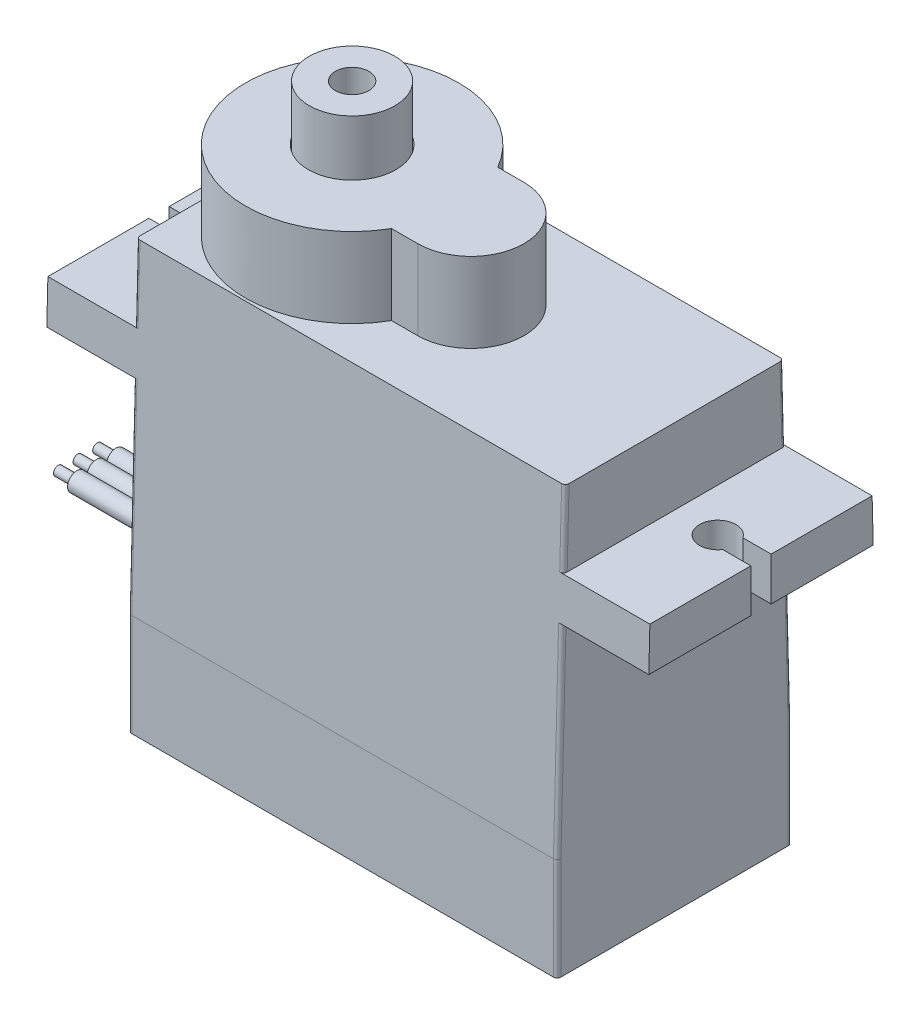
SolidWorks part; units mm, degrees
ref_plane "Front Plane" through (0, 0, 0) normal (0, 0, 1) x (1, 0, 0)
ref_plane "Top Plane" through (0, 0, 0) normal (0, 1, 0) x (1, 0, 0)
ref_plane "Right Plane" through (0, 0, 0) normal (1, 0, 0) x (0, 0, -1)
ref_axis "X-Axis" through (-88.99, 0, 0) along (1, 0, 0)
ref_axis "Y-Axis" through (0, 0, -88.99) along (0, 0, 1)
ref_axis "Z-Axis" through (0, 55, 0) along (0, -1, 0)
sketch "Sketch1" plane through (0, 0, 0) normal (0, 0, 1) x (1, 0, 0)
  line L0 (0, 0) -> (0, 12.96) construction
  line L1 (-7.1, 6.38) -> (15.93, 6.38)
  line L2 (-7.1, 6.38) -> (-7.1, 2.32)
  line L3 (-7.1, -16.34) -> (15.93, -16.34)
  line L4 (15.93, 6.38) -> (15.93, 2.32)
  line L5 (15.93, 2.32) -> (20.57, 2.32)
  line L6 (-11.74, 2.32) -> (-7.1, 2.32)
  line L7 (-11.74, 2.32) -> (-11.74, 0)
  line L8 (-11.74, 0) -> (-7.1, 0)
  line L9 (20.57, 2.32) -> (20.57, 0)
  line L10 (15.93, 0) -> (20.57, 0)
  line L11 (-7.1, 0) -> (-7.1, -16.34)
  line L12 (15.93, 0) -> (15.93, -16.34)
  line L14 (15.93, 0) -> (-7.1, 0) construction
  point P3 (4.415, 0)
  dimension "D1" = 2.32
  dimension "D2" = 32.31
  dimension "D3" = 23.03
  dimension "D4" = 16.34
  dimension "D5" = 22.72
  dimension "D6" = 7.1
  dimension "D7" = 15.93
  dimension "D10" = 29.3
  dimension "D11" = 4.415
extrude "Boss-Extrude1" add sketch "Sketch1" along normal mid plane 12.6
sketch "Sketch2" plane through (0, 6.38, 0) normal (0, 1, 0) x (1, 0, 0)
  line L0 (-1.375, 0) -> (5, 0) construction
  line L1 (3.5902, -2.85) -> (5, -2.85)
  line L2 (5, 2.85) -> (3.5902, 2.85)
  line L3 (-1.375, 0) -> (-7.1, 0) construction
  line L4 (5, 0) -> (7.85, 0) construction
  line L5 (-7.1, -6.3) -> (-7.1, 6.3) construction
  arc A0 (3.5902, 2.85) -> (3.5902, -2.85) centre (-1.375, 0) ccw
  arc A1 (5, -2.85) -> (5, 2.85) centre (5, 0) ccw
  dimension "D1" = 11.45
  dimension "D2" = 5.7
  dimension "D3" = 14.95
extrude "Boss-Extrude2" add sketch "Sketch2" along normal blind 4.28
sketch "Sketch11" plane through (-11.74, 0, 0) normal (-1, 0, 0) x (0, 0, 1)
  line L0 (-5.86, 6.38) -> (-6.3, -10.84)
  line L1 (0, 6.38) -> (-6.3, 6.38) construction
  line L2 (6.3, -16.34) -> (-6.3, -16.34) construction
  line L3 (-6.3, 0) -> (-6.3, -16.34) construction
  line L4 (-5.86, 6.38) -> (-6.3, 6.38)
  line L5 (-6.3, 6.38) -> (-6.3, -10.84)
  dimension "D1" = 5.86
  dimension "D2" = 5.5
extrude "Cut-Extrude4" cut sketch "Sketch11" against normal through all
mirror "Mirror1" about plane through (0, 0, 0) normal (0, 0, 1) of "Cut-Extrude4"
sketch "Sketch4" plane through (0, 0, 0) normal (0, 1, 0) x (1, 0, 0)
  line L0 (-7.1, 0) -> (-9.42, 0) construction
  line L1 (-11.74, -5.9637) -> (-11.74, 5.9637) construction
  line L2 (-10.2285, 0.545) -> (-11.74, 0.545)
  line L3 (-10.2285, 0.545) -> (-10.2285, -0.545)
  line L4 (-10.2285, -0.545) -> (-11.74, -0.545)
  line L5 (-11.74, 0.545) -> (-11.74, -0.545)
  line L8 (-9.42, 0) -> (-10.2285, 0) construction
  line L9 (-9.42, 0) -> (-11.74, 0) construction
  arc A0 (3.5902, 2.85) -> (3.5902, -2.85) centre (-1.375, 0) ccw construction
  circle A1 centre (-9.42, 0) radius 0.975
  dimension "D1" = 1.09
  dimension "D2" = 1.95
extrude "Cut-Extrude1" cut sketch "Sketch4" along normal through all contours A1 | L4 L5 L2 L3
sketch "Sketch14" plane through (0, 0.1538, 6.0191) normal (0, 0.0255, 0.9997) x (1, 0, 0)
  line L0 (4.415, -10.9974) -> (-7.1, -10.9974) construction
  line L1 (15.93, -10.9974) -> (-7.1, -10.9974) construction
ref_plane "Plane1" through (4.415, -10.84, 6.3) normal (-1, 0, 0) x (0, 0, 1)
mirror "Mirror2" about plane through (4.415, -10.84, 6.3) normal (-1, 0, 0) of "Cut-Extrude1"
sketch "Sketch5" plane through (0, -16.34, 0) normal (0, -1, 0) x (1, 0, 0)
  line L0 (15.93, 6.3) -> (-7.1, -6.3) construction
  line L17 (-5.46, 4.35) -> (14.29, 4.35) construction
  line L18 (-5.46, 4.35) -> (-5.46, -4.35) construction
  line L19 (-5.46, -4.35) -> (14.29, -4.35) construction
  line L20 (14.29, 4.35) -> (14.29, -4.35) construction
  line L21 (-5.46, 4.35) -> (14.29, -4.35) construction
  circle A0 centre (-5.46, 4.35) radius 1
  circle A1 centre (-5.46, -4.35) radius 1
  circle A2 centre (14.29, -4.35) radius 1
  circle A3 centre (14.29, 4.35) radius 1
  circle A4 centre (-5.46, 4.35) radius 0.975
  circle A5 centre (-5.46, -4.35) radius 0.975
  circle A6 centre (14.29, -4.35) radius 0.975
  circle A7 centre (14.29, 4.35) radius 0.975
  point P36 (4.415, 0)
  dimension "D1" = 0.025
  dimension "D4" = 1.95
  dimension "D5" = 19.75
  dimension "D6" = 8.7
extrude "Cut-Extrude2" cut sketch "Sketch5" against normal blind 1
sketch "Sketch6" plane through (-7.1, 0, 0) normal (-1, 0, 0) x (0, 0, 1)
  line L0 (-1.05, -11.34) -> (1.05, -11.34) construction
  line L1 (0, -11.84) -> (0, -16.34) construction
  line L3 (6.3, -16.34) -> (-6.3, -16.34) construction
  circle A0 centre (0, -11.34) radius 0.5
  circle A1 centre (1.05, -11.34) radius 0.5
  circle A2 centre (-1.05, -11.34) radius 0.5
  dimension "D3" = 1
  dimension "D1" = 4.5
  dimension "D2" = 2.1
extrude "Boss-Extrude4" add sketch "Sketch6" along normal blind 8
sketch "Sketch7" plane through (-15.1, 0, 0) normal (-1, 0, 0) x (0, 0, 1)
  circle A0 centre (0, -11.34) radius 0.25
  circle A1 centre (1.05, -11.34) radius 0.25
  circle A2 centre (-1.05, -11.34) radius 0.25
  dimension "D1" = 0.5
extrude "Boss-Extrude5" add sketch "Sketch7" along normal blind 1
sketch "Sketch3" plane through (0, 10.66, 0) normal (0, 1, 0) x (1, 0, 0)
  line L0 (4.7684, -0.55) -> (5, -0.55)
  line L1 (5, 0.55) -> (4.7684, 0.55)
  line L2 (5.55, 0) -> (7.85, 0) construction
  line L3 (-4.8, 0) -> (-7.1, 0) construction
  arc A0 (4.7684, 0.55) -> (4.7684, -0.55) centre (0, 0) ccw
  arc A1 (5, -0.55) -> (5, 0.55) centre (5, 0) ccw
  arc A2 (5, -2.85) -> (5, 2.85) centre (5, 0) ccw construction
  arc A3 (3.5902, 2.85) -> (3.5902, -2.85) centre (-1.375, 0) ccw construction
  dimension "D1" = 9.6
fillet "Fillet1" radius 0.3 4 edges at (14.29, -16.34, -5.325) (14.29, -16.34, 3.375) (-5.46, -16.34, -5.325) (-5.46, -16.34, 3.375)
fillet "Fillet3" radius 0.2 12 edges at (15.93, -13.59, -6.3) (15.93, -13.59, 6.3) (-7.1, -13.59, -6.3) (-7.1, -13.59, 6.3) (-7.1, -5.42, 6.1615) (-7.1, -5.42, -6.1615) (15.93, -5.42, 6.1615) (15.93, -5.42, -6.1615) (15.93, 4.35, -5.9119) (15.93, 4.35, 5.9119) (-7.1, 4.35, -5.9119) (-7.1, 4.35, 5.9119)
sketch "Sketch12" plane through (0, 10.66, 0) normal (0, 1, 0) x (1, 0, 0)
  circle A0 centre (-1.375, 0) radius 2.3
  circle A1 centre (-1.375, 0) radius 0.9
  dimension "D1" = 4.6
  dimension "D2" = 1.8
extrude "Boss-Extrude6" add sketch "Sketch12" along normal blind 2.95 and the other way blind 1 separate body
sketch "Sketch13" plane through (0, 13.61, 0) normal (0, 1, 0) x (1, 0, 0)
  circle A0 centre (-1.375, 0) radius 2.35
  dimension "D1" = 4.7
extrude "Cut-Extrude5" cut sketch "Sketch13" against normal blind 5
ref_axis "Axis1" through (-1.375, 9.66, 0) along (0, 1, 0)
